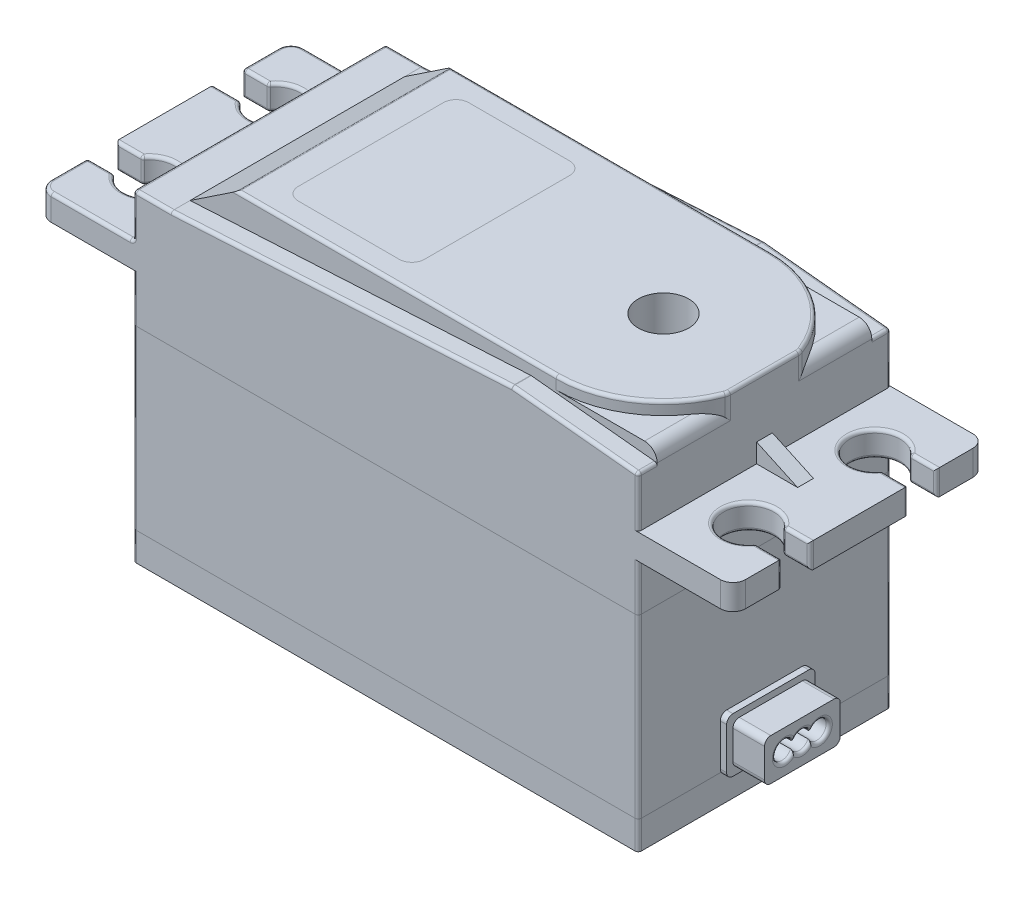
SolidWorks part; units mm, degrees
ref_plane "Front Plane" through (0, 0, 0) normal (0, 0, 1) x (1, 0, 0)
ref_plane "Top Plane" through (0, 0, 0) normal (0, 1, 0) x (1, 0, 0)
ref_plane "Right Plane" through (0, 0, 0) normal (1, 0, 0) x (0, 0, -1)
sketch "Sketch1" plane through (0, 0, 0) normal (0, 0, 1) x (1, 0, 0)
  line L1 (-20, -14) -> (20, -14)
  line L2 (-20, -14) -> (-20, 14)
  line L3 (-20, 14) -> (20, 14)
  line L4 (20, -14) -> (20, 14)
  line L5 (-20, -14) -> (20, 14) construction
  line L6 (-20, 14) -> (20, -14) construction
  point P0 (0, 0)
  dimension "D1" = 28
  dimension "D2" = 40
extrude "Boss-Extrude1" add sketch "Sketch1" along normal blind 20
sketch "Sketch2" plane through (20, 0, 0) normal (1, 0, 0) x (0, 0, -1)
  line L0 (-20, 6) -> (0, 6)
  line L1 (-20, -14) -> (-20, 14) construction
  line L2 (0, -14) -> (0, 14) construction
  line L4 (-20, 8) -> (0, 8)
  line L5 (-20, 8) -> (-20, 6)
  line L6 (0, 6) -> (0, 8)
  line L7 (-20, -14) -> (0, -14) construction
  dimension "D1" = 20
  dimension "D2" = 2
extrude "Boss-Extrude2" add sketch "Sketch2" along normal blind 7.5
mirror "Mirror1" about plane through (0, 0, 0) normal (1, 0, 0) of "Boss-Extrude2"
sketch "Sketch3" plane through (0, 14, 0) normal (0, 1, 0) x (1, 0, 0)
  line L0 (12, 0) -> (12, -20)
  line L1 (20, 0) -> (-20, 0) construction
  line L2 (20, -20) -> (-20, -20) construction
  line L4 (12, -10) -> (33, -10) construction
  line L5 (12, -6) -> (38, -6)
  line L6 (38, -6) -> (38, -14)
  line L7 (38, -14) -> (12, -14)
  line L8 (20, -20) -> (20, 0) construction
  line M9 (20, -20) -> (20, 0)
  dimension "D1" = 8
  dimension "D2" = 21
  dimension "D3" = 8
  dimension "D4" = 26
extrude "Boss-Extrude3" [suppressed] add sketch "Sketch3" along normal blind 6 contours L4 L0 L7 M9 | L4 L6 L5 M9 | L4 L7 L6 M9 | L0 L4 L5 M9
sketch "Sketch4" [suppressed] plane through (0, 20, 0) normal (0, 1, 0) x (1, 0, 0)
  circle A0 centre (33, -10) radius 1.5
  point P0 (33, -10)
  dimension "D1" = 3
extrude "Cut-Extrude1" [suppressed] cut sketch "Sketch4" against normal through all
sketch "Sketch5" plane through (0, -14, 0) normal (0, -1, 0) x (1, 0, 0)
  line L0 (-20, 10) -> (20, 10) construction
  line L4 (-20, 0) -> (20, 0)
  line L5 (20, 0) -> (20, 20)
  line L6 (20, 20) -> (-20, 20)
  line L7 (-20, 20) -> (-20, 0)
  line L8 (-20, 0) -> (20, 0)
  line L9 (20, 0) -> (20, 20)
  line L10 (20, 20) -> (-20, 20)
  line L11 (-20, 20) -> (-20, 0)
  point P6 (33, 10)
  dimension "D1" = 0
sketch "Sketch6" plane through (0, 14, 0) normal (0, 1, 0) x (1, 0, 0)
  line L0 (12, 0) -> (12, -20) construction
  circle A0 centre (12, -10) radius 2
  point P0 (12, -10)
  dimension "D1" = 4
extrude "Cut-Extrude2" cut sketch "Sketch6" against normal blind 10
sketch "Sketch7" plane through (0, 8, 0) normal (0, 1, 0) x (1, 0, 0)
  line L0 (-27.5, -10) -> (-20, -10) construction
  line L1 (-27.5, 0) -> (-27.5, -20) construction
  line L2 (-20, 0) -> (-20, -20) construction
  line L3 (-23.75, 0) -> (-23.75, -20) construction
  line L4 (-27.5, 0) -> (-20, 0) construction
  line L5 (-27.5, -20) -> (-20, -20) construction
  line L6 (-23.75, -5) -> (-27.5, -5) construction
  line L7 (-27.5, -3.875) -> (-25.4036, -3.875)
  line L8 (-27.5, -6.125) -> (-25.4036, -6.125)
  line L9 (-27.5, -13.875) -> (-25.4036, -13.875)
  line L10 (-27.5, -16.125) -> (-25.4036, -16.125)
  line L11 (0, 0) -> (0, -20) construction
  line L12 (20, -20) -> (-20, -20) construction
  line L13 (27.5, -16.125) -> (25.4036, -16.125)
  line L14 (27.5, -13.875) -> (25.4036, -13.875)
  line L15 (27.5, -6.125) -> (25.4036, -6.125)
  line L16 (27.5, -3.875) -> (25.4036, -3.875)
  line L17 (-27.5, -3.875) -> (-27.5, -6.125)
  line L18 (-27.5, -13.875) -> (-27.5, -16.125)
  line L19 (27.5, -3.875) -> (27.5, -6.125)
  line L20 (27.5, -16.125) -> (27.5, -13.875)
  arc A0 (-25.4036, -6.125) -> (-25.4036, -3.875) centre (-23.75, -5) ccw
  arc A1 (-25.4036, -16.125) -> (-25.4036, -13.875) centre (-23.75, -15) ccw
  arc A2 (25.4036, -16.125) -> (25.4036, -13.875) centre (23.75, -15) cw
  arc A3 (25.4036, -6.125) -> (25.4036, -3.875) centre (23.75, -5) cw
  dimension "D2" = 4
  dimension "D1" = 10
  dimension "D3" = 2.25
extrude "Cut-Extrude3" cut sketch "Sketch7" against normal up to surface (2 mm away) up to face at (23.75, 6, 10)
fillet "Fillet1" radius 1 4 edges at (-27.5, 7, 0) (-27.5, 7, 20) (27.5, 7, 20) (27.5, 7, 0)
sketch3d "3DSketch1" plane through (0, 0, 0) normal (0, 0, 1) x (1, 0, 0)
  dimension "D1" = 10
sketch "Sketch8" plane through (0, 0, 10) normal (0, 0, 1) x (1, 0, 0)
  line L0 (-20, 14) -> (-20, 8) construction
  line L1 (-26.5, 8) -> (-20, 8) construction
  line L2 (-20, 14) -> (-20, 8)
  line L3 (-26.5, 8) -> (-20, 8)
  line L4 (-20, 9.5) -> (-23.25, 8)
  line L5 (0, 0) -> (0, 16.0906) construction
  line L6 (26.5, 8) -> (20, 8)
  line L7 (20, 14) -> (20, 8)
  line L8 (20, 9.5) -> (23.25, 8)
  dimension "D1" = 1.5
extrude "Boss-Extrude4" add sketch "Sketch8" along normal mid plane 1.25 contours L8 L7 L6 | L2 L4 L3 region at (-21.0833, 8.5, 10) region at (21.0833, 8.5, 10)
sketch "Sketch9" plane through (0, 0, 20) normal (0, 0, 1) x (1, 0, 0)
  line L0 (-20, 14) -> (-20, 8) construction
  line L1 (-20, 14) -> (-20, 8)
  line L2 (14, 14) -> (10, 14) construction
  line L3 (14, 14) -> (10, 14)
  line L4 (-20, 11.5) -> (-17, 11.5)
  line L5 (10, 13) -> (20, 12)
  line L6 (20, 8) -> (20, 14) construction
  line L7 (20, 14) -> (-20, 14) construction
  line L8 (-20, 14) -> (20, 14)
  line L9 (20, 14) -> (20, 12)
  line L10 (-26.5, 8) -> (-20, 8) construction
  line L11 (-17, 11.5) -> (10, 13)
  line M6 (20, 8) -> (20, 14)
  line M7 (20, 14) -> (-20, 14)
  line M8 (-20, 14) -> (-20, 8)
  dimension "D1" = 3
  dimension "D2" = 1
  dimension "D3" = 2
  dimension "D4" = 3.5
extrude "Cut-Extrude4" cut sketch "Sketch9" against normal blind 1.5 contours L5 M6 M7 M8 region at (-2.3214, 13.0693, 20)
sketch "Sketch10" plane through (0, 0, 0) normal (0, 0, -1) x (-1, 0, 0)
  line L0 (-20, 14) -> (-20, 12) construction
  line L1 (20, 14) -> (20, 8) construction
  line L2 (20, 11.5) -> (17, 11.5) construction
  line L3 (20, 14) -> (-20, 14) construction
  line L4 (17, 11.5) -> (-10, 13) construction
  line L5 (-10, 13) -> (-20, 12) construction
  line L6 (-20, 14) -> (-20, 12)
  line L7 (20, 14) -> (20, 8)
  line L8 (20, 11.5) -> (17, 11.5)
  line L9 (20, 14) -> (-20, 14)
  line L10 (17, 11.5) -> (-10, 13)
  line L11 (-10, 13) -> (-20, 12)
  line M11 (20, 14) -> (-20, 14)
  line M12 (-20, 14) -> (-20, 8)
extrude "Cut-Extrude5" cut sketch "Sketch10" against normal blind 1.5 contours L11 L10 L8 L7 M11 M12 region at (-2.3214, 13.0693, 0)
sketch "Sketch11" plane through (0, 0, 18.5) normal (0, 0, 1) x (1, 0, 0)
  line L0 (-20, 11.5) -> (-17, 11.5) construction
  line L1 (-20, 11.5) -> (-17, 11.5)
  line L2 (-17, 11.5) -> (-13.2583, 14)
  line L3 (20, 14) -> (-20, 14) construction
  line L4 (-13.2583, 14) -> (-20, 14)
  line L5 (-20, 14) -> (-20, 11.5)
  dimension "D1" = 4.5
extrude "Cut-Extrude6" cut sketch "Sketch11" against normal up to surface (17 mm away) up to face at (-1.1667, 12.6667, 1.5)
sketch "Sketch12" plane through (0, 14, 0) normal (0, 1, 0) x (1, 0, 0)
  line L0 (20, -18.5) -> (20, -1.5) construction
  line L1 (20, -18.5) -> (20, -12.8723)
  line L3 (20, -18.5) -> (-13.2583, -18.5) construction
  line L4 (12, -1.5) -> (20, -1.5)
  line L5 (12, -18.5) -> (20, -18.5)
  line L6 (20, -7.1277) -> (20, -1.5)
  arc A0 (12, -18.5) -> (20, -12.8723) centre (12, -10) ccw
  arc A1 (20, -7.1277) -> (12, -1.5) centre (12, -10) ccw
extrude "Cut-Extrude7" cut sketch "Sketch12" against normal up to vertex (1 mm away) up to point (10, 13, 18.5)
fillet "Fillet2" radius 1 4 edges at (20, 13.5, 7.1277) (20, 13.5, 12.8723) (20, 13, 4.3139) (20, 13, 15.6861)
fillet "Fillet3" radius 0.25 19 edges at (-27.5, 8, 2.4375) (-27.5, 8, 17.5625) (-27.2071, 8, 0.2929) (-27.2071, 8, 19.7071) (-23.25, 8, 0) (-23.25, 8, 20) (10, 13, 0.75) (15, 12.5, 0) (-18.5, 11.5, 0) (-3.5, 12.25, 0) (10, 13, 19.25) (-20, 9.75, 0) (-20, 8, 15.3125) (-20, 8, 4.6875) (-20, 9.75, 20) (-20, 11.5, 10) (-18.5, 11.5, 20) (-3.5, 12.25, 20) (15, 12.5, 20)
fillet "Fillet4" radius 0.25 8 edges at (-0.6292, 14, 1.5) (-0.6292, 14, 18.5) (16.812, 14, 17.0067) (19.9832, 14, 12.8752) (20, 14, 10) (19.9832, 14, 7.1248) (-13.2583, 14, 10) (16.812, 14, 2.9933)
fillet "Fillet6" radius 0.25 42 edges at (21.75, 6, 5) (21.75, 8, 5) (21.75, 6, 15) (21.75, 8, 15) (25.4036, 7, 6.125) (25.4036, 7, 3.875) (27.5, 7, 3.875) (27.5, 7, 6.125) (27.5, 7, 13.875) (25.4036, 7, 13.875) (25.4036, 7, 16.125) (27.5, 7, 16.125) (-26.3268, 8, 3.875) (-27.4268, 7.9268, 3.875) (-26.3268, 8, 16.125) (-27.4268, 7.9268, 16.125) (26.4518, 6, 16.125) (26.4518, 8, 16.125) (26.4518, 6, 13.875) (26.4518, 8, 13.875) (26.4518, 6, 3.875) (26.4518, 8, 3.875) (26.4518, 6, 6.125) (26.4518, 8, 6.125) (-26.4518, 6, 6.125) (-27.5, 7, 6.125) (-25.4036, 7, 6.125) (-26.4518, 8, 6.125) (-27.5, 6.875, 3.875) (-26.4518, 6, 3.875) (-25.4036, 7, 3.875) (-21.75, 6, 5) (-21.75, 8, 5) (-26.4518, 6, 13.875) (-26.4518, 8, 13.875) (-26.4518, 6, 16.125) (-27.5, 6.875, 16.125) (-25.4036, 7, 16.125) (-27.5, 7, 13.875) (-25.4036, 7, 13.875) (-21.75, 6, 15) (-21.75, 8, 15)
sketch "Sketch13" plane through (20, 0, 0) normal (1, 0, 0) x (0, 0, -1)
  line L0 (-10, -14) -> (-10, 13.75) construction
  line L1 (-20, -14) -> (0, -14) construction
  line L2 (-7.3074, 13.75) -> (-12.6926, 13.75) construction
  line L3 (-13, -12) -> (-7, -12)
  line L4 (-6.5, -11.5) -> (-6.5, -8.2)
  line L5 (-7, -7.7) -> (-13, -7.7)
  line L6 (-13.5, -8.2) -> (-13.5, -11.5)
  arc A0 (-13, -12) -> (-13.5, -11.5) centre (-13, -11.5) cw
  arc A1 (-7, -12) -> (-6.5, -11.5) centre (-7, -11.5) ccw
  arc A2 (-6.5, -8.2) -> (-7, -7.7) centre (-7, -8.2) ccw
  arc A3 (-13, -7.7) -> (-13.5, -8.2) centre (-13, -8.2) ccw
  point P12 (-13.5, -12)
  point P17 (-6.5, -7.7)
  point P20 (-13.5, -7.7)
  dimension "D4" = 0.5
  dimension "D1" = 7
  dimension "D2" = 4.3
  dimension "D3" = 2
extrude "Boss-Extrude5" add sketch "Sketch13" along normal mid plane 1
sketch "Sketch14" plane through (20.5, 0, 0) normal (1, 0, 0) x (0, 0, -1)
  line L8 (-13, -11.5) -> (-7, -11.5)
  line L9 (-7, -11.5) -> (-7, -8.2)
  line L10 (-7, -8.2) -> (-13, -8.2)
  line L11 (-13, -8.2) -> (-13, -11.5)
  line L12 (-12.5, -11.5) -> (-7.5, -11.5)
  line L13 (-7, -11) -> (-7, -8.7)
  line L14 (-7.5, -8.2) -> (-12.5, -8.2)
  line L15 (-13, -8.7) -> (-13, -11)
  arc A4 (-12.5, -11.5) -> (-13, -11) centre (-12.5, -11) cw
  arc A5 (-7.5, -11.5) -> (-7, -11) centre (-7.5, -11) ccw
  arc A6 (-7, -8.7) -> (-7.5, -8.2) centre (-7.5, -8.7) ccw
  arc A7 (-12.5, -8.2) -> (-13, -8.7) centre (-12.5, -8.7) ccw
  dimension "D2" = 0.5
  dimension "D1" = 0.5
extrude "Boss-Extrude6" add sketch "Sketch14" along normal mid plane 5
sketch "Sketch15" plane through (23, 0, 0) normal (1, 0, 0) x (0, 0, -1)
  line L0 (-13, -9.85) -> (-7, -9.85) construction
  line L1 (-13, -8.7) -> (-13, -11) construction
  line L2 (-7, -11) -> (-7, -8.7) construction
  line L3 (-10, -8.2) -> (-10, -11.5) construction
  line L4 (-7.5, -8.2) -> (-12.5, -8.2) construction
  line L5 (-12.5, -11.5) -> (-7.5, -11.5) construction
  arc A0 (-10.6875, -10.1497) -> (-9.3125, -10.1497) centre (-10, -9.85) ccw
  arc A1 (-10.6875, -9.5503) -> (-10.6875, -10.1497) centre (-11.375, -9.85) ccw
  arc A2 (-9.3125, -10.1497) -> (-9.3125, -9.5503) centre (-8.625, -9.85) ccw
  arc A3 (-9.3125, -9.5503) -> (-10.6875, -9.5503) centre (-10, -9.85) ccw
  dimension "D1" = 1.5
  dimension "D2" = 2.75
extrude "Cut-Extrude8" cut sketch "Sketch15" against normal up to surface (2.5 mm away) up to face at (20.5, -9.85, 10)
fillet "Fillet7" radius 0.25 4 edges at (23, -9.85, 7.875) (23, -9.1, 10) (23, -9.85, 12.125) (23, -10.6, 10)
sketch "Sketch17" plane through (0, 0, 20) normal (0, 0, 1) x (1, 0, 0)
  line L0 (-20, 2.25) -> (20, 2.25)
  line L1 (-20, 6) -> (-20, -14) construction
  line L2 (20, -14) -> (20, 6) construction
  line L3 (-20, -11.75) -> (20, -11.75)
  line L4 (-20, -14) -> (20, -14) construction
  line L5 (-20, 2.25) -> (-20, -11.75)
  line L6 (20, -11.75) -> (20, 2.25)
  dimension "D1" = 14
  dimension "D2" = 2.25
split line "Split Line2"
sketch "Sketch18" plane through (-20, 0, 0) normal (-1, 0, 0) x (0, 0, 1)
  line L0 (20, 2.25) -> (20, -11.75) construction
  line L1 (20, 2.25) -> (20, -11.75)
  line L2 (20, 2.25) -> (0, 2.25)
  line L3 (0, 6) -> (0, -14) construction
  line L4 (0, 2.25) -> (0, -11.75)
  line L5 (0, -11.75) -> (20, -11.75)
split line "Split Line3"
sketch "Sketch19" plane through (0, 0, 0) normal (0, 0, -1) x (-1, 0, 0)
  line L4 (20, 2.25) -> (-20, 2.25)
  line L5 (-20, 2.25) -> (-20, -11.75)
  line L6 (-20, -11.75) -> (20, -11.75)
  line L7 (20, -11.75) -> (20, 2.25)
  line L8 (20, 2.25) -> (-20, 2.25)
  line L9 (-20, 2.25) -> (-20, -11.75)
  line L10 (-20, -11.75) -> (20, -11.75)
  line L11 (20, -11.75) -> (20, 2.25)
  dimension "D1" = 0
split line "Split Line4"
sketch "Sketch20" plane through (20, 0, 0) normal (1, 0, 0) x (0, 0, -1)
  line L4 (-20, 2.25) -> (-20, -11.75)
  line L5 (-20, -11.75) -> (0, -11.75)
  line L6 (0, -11.75) -> (0, 2.25)
  line L7 (0, 2.25) -> (-20, 2.25)
  line L8 (-20, 2.25) -> (-20, -11.75)
  line L9 (-20, -11.75) -> (0, -11.75)
  line L10 (0, -11.75) -> (0, 2.25)
  line L11 (0, 2.25) -> (-20, 2.25)
  dimension "D1" = 0
split line "Split Line5"
sketch "Sketch21" plane through (0, 14, 0) normal (0, 1, 0) x (1, 0, 0)
  line L0 (-13.1825, -10) -> (19.75, -10) construction
  line L1 (-13.1825, -1.75) -> (-13.1825, -18.25) construction
  line L2 (19.75, -12.6926) -> (19.75, -7.3074) construction
  line L3 (-11.1825, -4.25) -> (-11.1825, -15.75)
  line L4 (-13.1825, -18.25) -> (12, -18.25) construction
  line L5 (-10.1825, -3.25) -> (-2.1825, -3.25)
  line L6 (-1.1825, -4.25) -> (-1.1825, -15.75)
  line L7 (-2.1825, -16.75) -> (-10.1825, -16.75)
  arc A0 (-11.1825, -15.75) -> (-10.1825, -16.75) centre (-10.1825, -15.75) ccw
  arc A1 (-1.1825, -15.75) -> (-2.1825, -16.75) centre (-2.1825, -15.75) cw
  arc A2 (-2.1825, -3.25) -> (-1.1825, -4.25) centre (-2.1825, -4.25) cw
  arc A3 (-11.1825, -4.25) -> (-10.1825, -3.25) centre (-10.1825, -4.25) cw
  point P14 (-11.1825, -16.75)
  point P19 (-1.1825, -3.25)
  point P22 (-11.1825, -3.25)
  dimension "D4" = 1
  dimension "D1" = 2
  dimension "D2" = 1.5
  dimension "D3" = 10
split line "Split Line6"
fillet "Fillet8" radius 0.25 18 edges at (-20, 4.125, 20) (-20, -4.75, 20) (-20, -12.875, 20) (20, 12, 19.125) (20, 11.9264, 19.9268) (20, -12.875, 20) (20, -4.75, 20) (20, 4.125, 20) (20, 12, 0.875) (20, 11.9264, 0.0732) (-20, 4.125, 0) (-20, -4.75, 0) (-20, -12.875, 0) (20, -12.875, 0) (20, -4.75, 0) (20, 4.125, 0) (20, 9.8744, 20) (20, 9.8744, 0)
